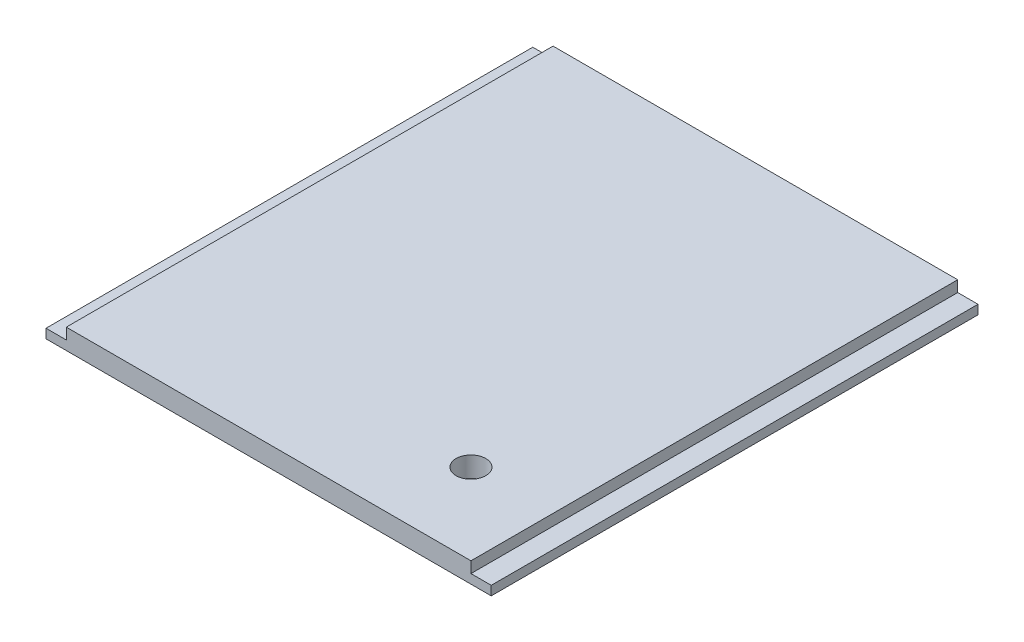
SolidWorks part; units mm, degrees
ref_plane "Front Plane" through (0, 0, 0) normal (0, 0, 1) x (1, 0, 0)
ref_plane "Top Plane" through (0, 0, 0) normal (0, 1, 0) x (1, 0, 0)
ref_plane "Right Plane" through (0, 0, 0) normal (1, 0, 0) x (0, 0, -1)
sketch "Sketch1" plane through (0, 0, 0) normal (0, 1, 0) x (1, 0, 0)
  line L1 (0, 0) -> (139.4003, 0)
  line L2 (0, 0) -> (0, 152.4)
  line L3 (0, 152.4) -> (139.4003, 152.4)
  line L4 (139.4003, 0) -> (139.4003, 152.4)
  dimension "D1" = 152.4
  dimension "D2" = 139.4003
extrude "Boss-Extrude1" add sketch "Sketch1" along normal blind 6.35
sketch "Sketch2" plane through (0, 6.35, 0) normal (0, 1, 0) x (1, 0, 0)
  line L0 (0, 0) -> (139.4003, 0) construction
  line L1 (0, 152.4) -> (6.35, 152.4)
  line L2 (0, 152.4) -> (0, 0)
  line L3 (0, 0) -> (6.35, 0)
  line L4 (6.35, 152.4) -> (6.35, 0)
  line L6 (139.4003, 152.4) -> (133.0503, 152.4)
  line L7 (139.4003, 152.4) -> (139.4003, 0)
  line L8 (139.4003, 0) -> (133.0503, 0)
  line L9 (133.0503, 152.4) -> (133.0503, 0)
  dimension "D1" = 6.35
  dimension "D2" = 6.35
extrude "Cut-Extrude1" cut sketch "Sketch2" against normal blind 3.4747
sketch "Sketch3" plane through (0, 6.35, 0) normal (0, 1, 0) x (1, 0, 0)
  line L0 (6.35, 0) -> (133.0503, 0) construction
  line L2 (133.0503, 152.4) -> (133.0503, 0) construction
  circle A0 centre (107.6503, 25.4) radius 4.6584
  point P2 (0, 0)
  dimension "D1" = 9.3167
  dimension "D2" = 25.4
  dimension "D3" = 25.4
extrude "Cut-Extrude2" cut sketch "Sketch3" against normal through all
